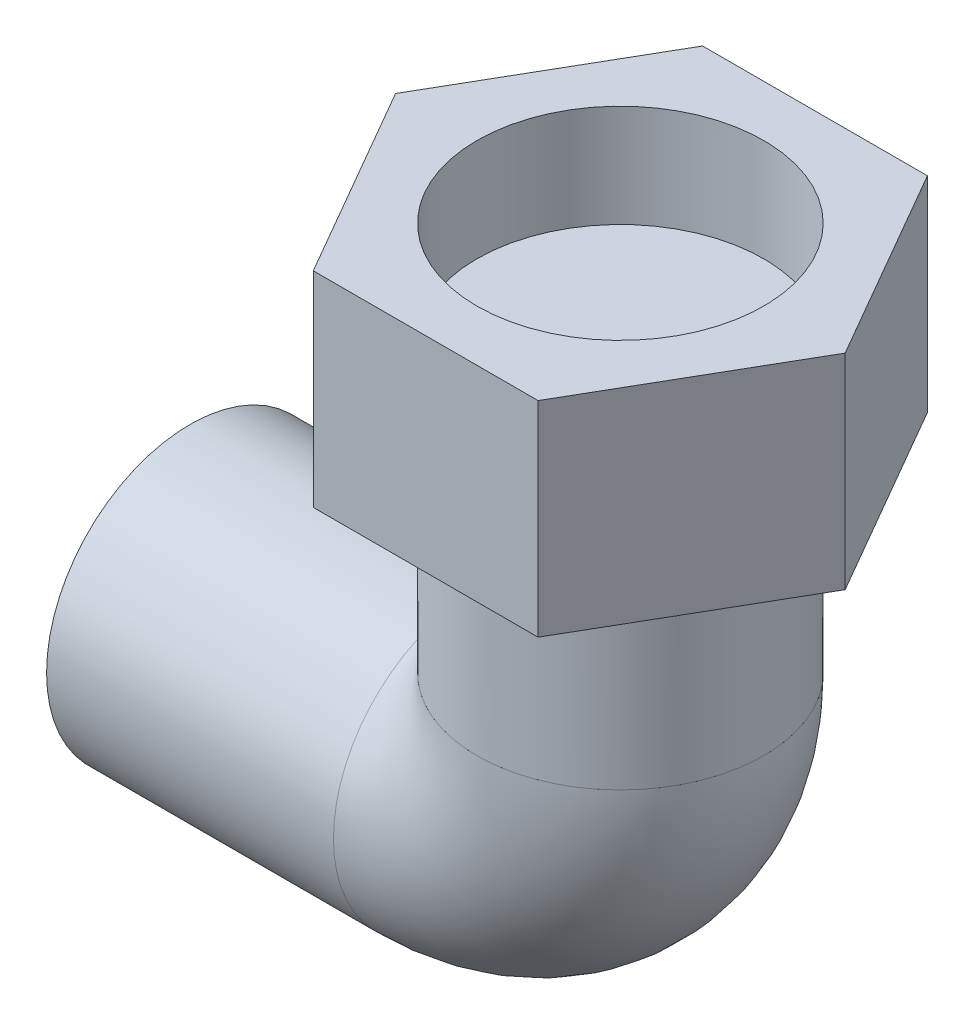
SolidWorks part; units mm, degrees
ref_plane "Front Plane" through (0, 0, 0) normal (0, 0, 1) x (1, 0, 0)
ref_plane "Top Plane" through (0, 0, 0) normal (0, 1, 0) x (1, 0, 0)
ref_plane "Right Plane" through (0, 0, 0) normal (1, 0, 0) x (0, 0, -1)
sketch "Szkic1" plane through (0, 0, 0) normal (0, 0, 1) x (1, 0, 0)
  line L0 (0, 0) -> (14, 0)
  line L1 (28, 14) -> (28, 28)
  line L2 (14, 28) -> (14, 14)
  line L3 (14, 28) -> (28, 28)
  line L4 (21, 28) -> (21, 14)
  line L5 (0, 0) -> (0, 14)
  line L6 (0, 7) -> (14, 7)
  line L7 (14, 14) -> (0, 14)
  line L8 (14, 14) -> (28, 14)
  line L9 (14, 14) -> (14, 0)
  line L10 (0, 7) -> (0, 12)
  line L12 (0, 7) -> (0, 2)
  line L15 (0, 7) -> (-9.3849, 7)
  line L19 (-9.3849, 7) -> (-9.3849, 2)
  line L20 (-9.3849, 2) -> (0, 2)
  arc A0 (14, 0) -> (28, 14) centre (14, 14) ccw
  arc A1 (14, 7) -> (21, 14) centre (14, 14) ccw
  dimension "D2" = 14
  dimension "D1" = 14
  dimension "D3" = 14
  dimension "D4" = 5
  dimension "D5" = 5
revolve "Obrót1" add sketch "Szkic1" angle 360 about L4 region at (24.5, 21, 0)
revolve "Obrót2" add sketch "Szkic1<4>" angle 360 about L6 region at (7, 10.5, 0)
sketch "Szkic1<4>" plane through (0, 0, 0) normal (0, 0, 1) x (1, 0, 0) same geometry as "Szkic1"
sketch "Szkic5" plane through (14, 0, 0) normal (1, 0, 0) x (0, 0, -1)
  line L1 (0, 14) -> (-8.4154, 14)
  line L2 (-8.4154, 14) -> (8.105, 14)
  line L3 (-0.8701, 13.9457) -> (0.9526, 13.9349)
  circle A0 centre (0, 7) radius 7 construction
  circle A1 centre (0, 7) radius 7
  dimension "D1" = 14
revolve "Obrót10" add sketch "Szkic5" angle 90 about L2 region at (14, 6.9967, 0) reverse direction yes
sketch "Szkic7" plane through (0, 28, 0) normal (0, 1, 0) x (1, 0, 0)
  line L0 (0, 0) -> (14, 0)
  line L1 (14, 0) -> (21, 0)
  line L3 (10.0303, 0) -> (15.5152, -9.5)
  line L4 (15.5152, -9.5) -> (26.4848, -9.5)
  line L5 (26.4848, -9.5) -> (31.9697, 0)
  line L6 (31.9697, 0) -> (26.4848, 9.5)
  line L7 (26.4848, 9.5) -> (15.5152, 9.5)
  line L8 (15.5152, 9.5) -> (10.0303, 0)
  circle A0 centre (21, 0) radius 7 construction
  circle A1 centre (21, 0) radius 9.5 construction
  circle A2 centre (21, 0) radius 8.4068
  circle M3 centre (21, 0) radius 7
  dimension "D1" = 19
extrude "Dodanie-wyciągnięcie1" add sketch "Szkic7" along normal blind 5 and the other way blind 5 contours L7 L8 L3 L4 L5 L6 M3 | M3 | A2 region at (21, 28, -6.802) region at (13.0241, 28, -4.6049)
